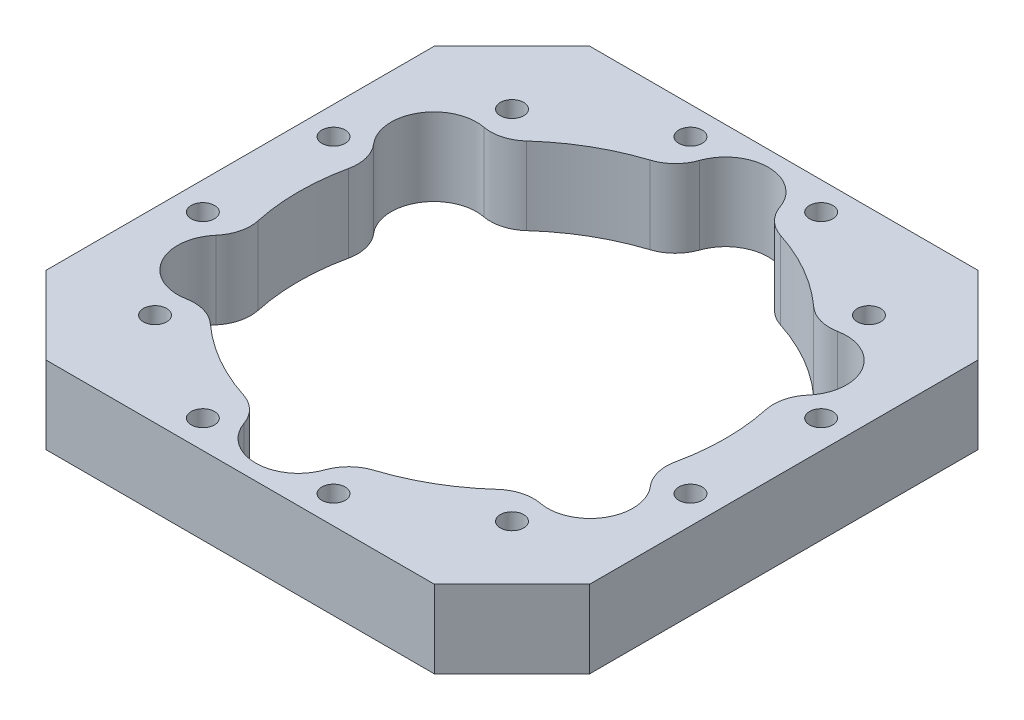
SolidWorks part; units mm, degrees
ref_plane "Front Plane" through (0, 0, 0) normal (0, 0, 1) x (1, 0, 0)
ref_plane "Top Plane" through (0, 0, 0) normal (0, 1, 0) x (1, 0, 0)
ref_plane "Right Plane" through (0, 0, 0) normal (1, 0, 0) x (0, 0, -1)
sketch "Sketch1" plane through (0, 0, 0) normal (0, 1, 0) x (1, 0, 0)
  line L0 (-49.1682, 0) -> (0, 0) construction
  line L1 (0, 0) -> (-48.4521, -12.9827) construction
  line L2 (-35, 35) -> (35, 35)
  line L3 (-35, 35) -> (-35, -35)
  line L4 (35, 35) -> (35, -35)
  line L5 (-35, -35) -> (35, -35)
  circle A0 centre (0, 0) radius 35 construction
  circle A1 centre (0, 0) radius 32.5 construction
  circle A2 centre (0, 0) radius 27.5
  circle A3 centre (0, 27.5) radius 5.5
  circle A4 centre (23.8157, 13.75) radius 5.5
  circle A5 centre (23.8157, -13.75) radius 5.5
  circle A6 centre (0, -27.5) radius 5.5
  circle A7 centre (-23.8157, -13.75) radius 5.5
  circle A8 centre (-23.8157, 13.75) radius 5.5
  circle A9 centre (-31.3926, -8.4116) radius 1.5
  circle A10 centre (-31.3926, 8.4116) radius 1.5
  circle A11 centre (-22.981, 22.981) radius 1.5
  circle A12 centre (-8.4116, 31.3926) radius 1.5
  circle A13 centre (8.4116, 31.3926) radius 1.5
  circle A14 centre (22.981, 22.981) radius 1.5
  circle A15 centre (31.3926, 8.4116) radius 1.5
  circle A16 centre (31.3926, -8.4116) radius 1.5
  circle A17 centre (22.981, -22.981) radius 1.5
  circle A18 centre (8.4116, -31.3926) radius 1.5
  circle A19 centre (-8.4116, -31.3926) radius 1.5
  circle A20 centre (-22.981, -22.981) radius 1.5
  point P19 (0, 0)
  point P47 (0, 0)
  dimension "D1" = 70
  dimension "D2" = 65
  dimension "D3" = 55
  dimension "D4" = 11
  dimension "D7" = 3
  dimension "D6" = 15
  dimension "D5" = 6
  dimension "D8" = 12
extrude "Boss-Extrude1" add sketch "Sketch1" along normal blind 10 contours A0 A20 A19 A18 A17 A16 A15 A14 A13 A12 A11 A10 A9 A8 A2 A3 A4 A5 A6 A7 region at (0, 0, -34.0101)
fillet "Fillet1" radius 5 12 edges at (5.4724, 5, -26.95) (20.6032, 5, -18.2143) (26.0756, 5, 8.7357) (26.0756, 5, -8.7357) (20.6032, 5, 18.2143) (5.4724, 5, 26.95) (-5.4724, 5, 26.95) (-20.6032, 5, 18.2143) (-26.0756, 5, 8.7357) (-26.0756, 5, -8.7357) (-20.6032, 5, -18.2143) (-5.4724, 5, -26.95)
chamfer "Chamfer1" distance 10 angle 45 4 edges at (-35, 5, 35) (35, 5, 35) (35, 5, -35) (-35, 5, -35)
